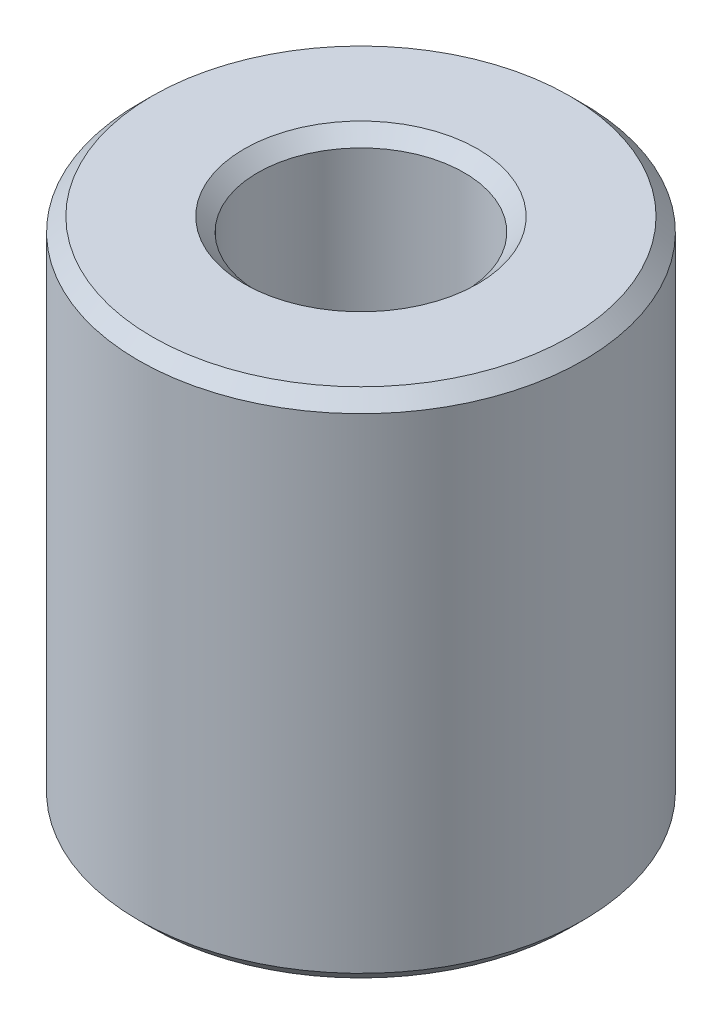
SolidWorks part; units mm, degrees
ref_plane "Front Plane" through (0, 0, 0) normal (0, 0, 1) x (1, 0, 0)
ref_plane "Top Plane" through (0, 0, 0) normal (0, 1, 0) x (1, 0, 0)
ref_plane "Right Plane" through (0, 0, 0) normal (1, 0, 0) x (0, 0, -1)
sketch "Sketch1" plane through (0, 0, 0) normal (0, 1, 0) x (1, 0, 0)
  circle A0 centre (0, 0) radius 10
  dimension "SLEEVE_OD" = 20
extrude "Boss-Extrude1" add sketch "Sketch1" along normal blind 23.0282
sketch "Sketch2" plane through (0, 0, 0) normal (0, 1, 0) x (1, 0, 0)
  circle A0 centre (0, 0) radius 4.6408
  dimension "BORE_D" = 9.2817
extrude "Cut-Extrude1" cut sketch "Sketch2" along normal through all
chamfer "Chamfer1" distance 0.6142 angle 45 4 edges at (0, 23.0282, 4.6408) (0, 0, 4.6408) (0, 0, 10) (0, 23.0282, 10)
